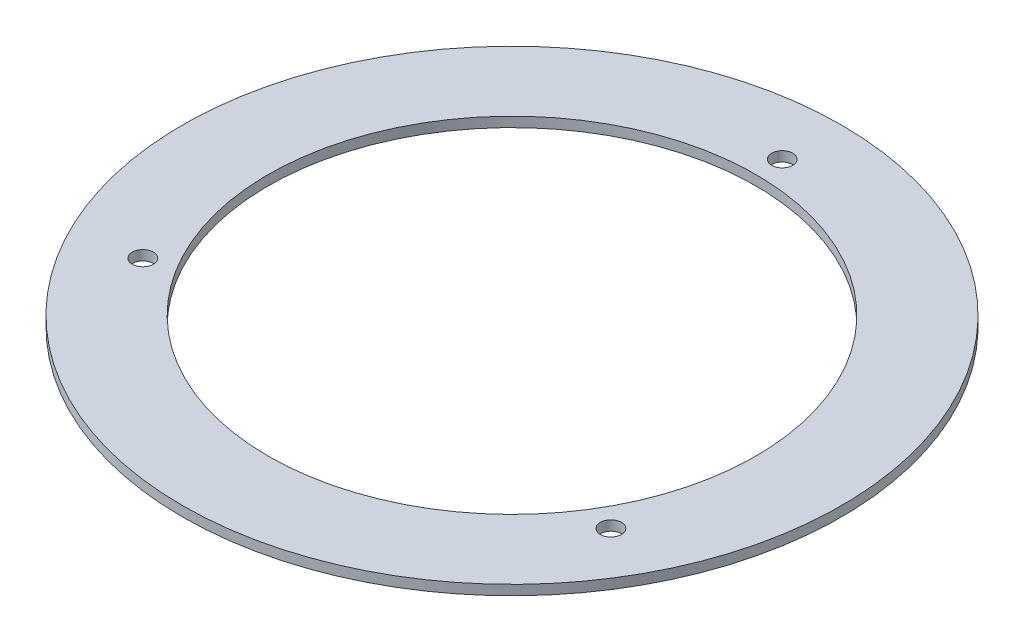
SolidWorks part; units mm, degrees
note: The reader was unsure of these and kept them because the rebuilt part matched: thickness of "Base-Flange1", "Sheet-Metal1", "Sheet-Metal2".
ref_plane "Front Plane" through (0, 0, 0) normal (0, 0, 1) x (1, 0, 0)
ref_plane "Top Plane" through (0, 0, 0) normal (0, 1, 0) x (1, 0, 0)
ref_plane "Right Plane" through (0, 0, 0) normal (1, 0, 0) x (0, 0, -1)
sketch "Sketch1" plane through (0, 0, 0) normal (0, 1, 0) x (1, 0, 0)
  circle A0 centre (0, 0) radius 37
  circle A1 centre (0, 0) radius 50
  dimension "D1" = 74
  dimension "D2" = 100
base flange "Base-Flange1" sketch "Sketch1" thickness 1.5 reverse thickness direction no parameters "D1"=1.5
sketch "Sketch6" plane through (0, 0, 0) normal (0, 1, 0) x (1, 0, 0)
  line L0 (0, 0) -> (0, 41) construction
  line L1 (0, 0) -> (35.507, -20.5) construction
  line L2 (0, 0) -> (-35.507, -20.5) construction
  circle A5 centre (0, 41) radius 1.6
  circle A6 centre (35.507, -20.5) radius 1.6
  circle A7 centre (-35.507, -20.5) radius 1.6
  point P9 (0, 0)
  dimension "D1" = 41
  dimension "D2" = 3.2
  dimension "D3" = 3
extrude "Cut-Extrude1" cut sketch "Sketch6" against normal through all normal cut yes
sketch "Bend-Lines1" [suppressed] plane through (0, 0, 0) normal (0, 1, 0) x (1, 0, 0)
sketch "Bounding-Box1" [suppressed] plane through (0, 0, 0) normal (0, 1, 0) x (1, 0, 0)
sheet metal parameters "Sheet-Metal1" thickness 1.5 parameters "D1"=2, "D7"=2
flat pattern "Flat-Pattern1" [suppressed]
sketch "Bend-Lines2" plane through (0, 0, 0) normal (0, 1, 0) x (1, 0, 0)
sketch3d "Bounding-Box2" [suppressed]
  line L0 (50.0306, 49.9694, 0) -> (49.9694, -50.0306, 0) construction
  line L1 (-49.9694, 50.0306, 0) -> (-50.0306, -49.9694, 0) construction
  line L2 (50.0306, 49.9694, 0) -> (-49.9694, 50.0306, 0) construction
  line L3 (49.9694, -50.0306, 0) -> (-50.0306, -49.9694, 0) construction
sheet metal parameters "Sheet-Metal2" thickness 1.5 parameters "D1"=2, "D7"=2
flat pattern "Flat-Pattern1"
sketch "Bend-Lines2" plane through (0, 0, 0) normal (0, 1, 0) x (1, 0, 0)
sketch3d "Bounding-Box2" [suppressed]
  line L0 (-50.0306, 49.9694, 0) -> (-49.9694, -50.0306, 0) construction
  line L1 (49.9694, 50.0306, 0) -> (50.0306, -49.9694, 0) construction
  line L2 (-50.0306, 49.9694, 0) -> (49.9694, 50.0306, 0) construction
  line L3 (-49.9694, -50.0306, 0) -> (50.0306, -49.9694, 0) construction
